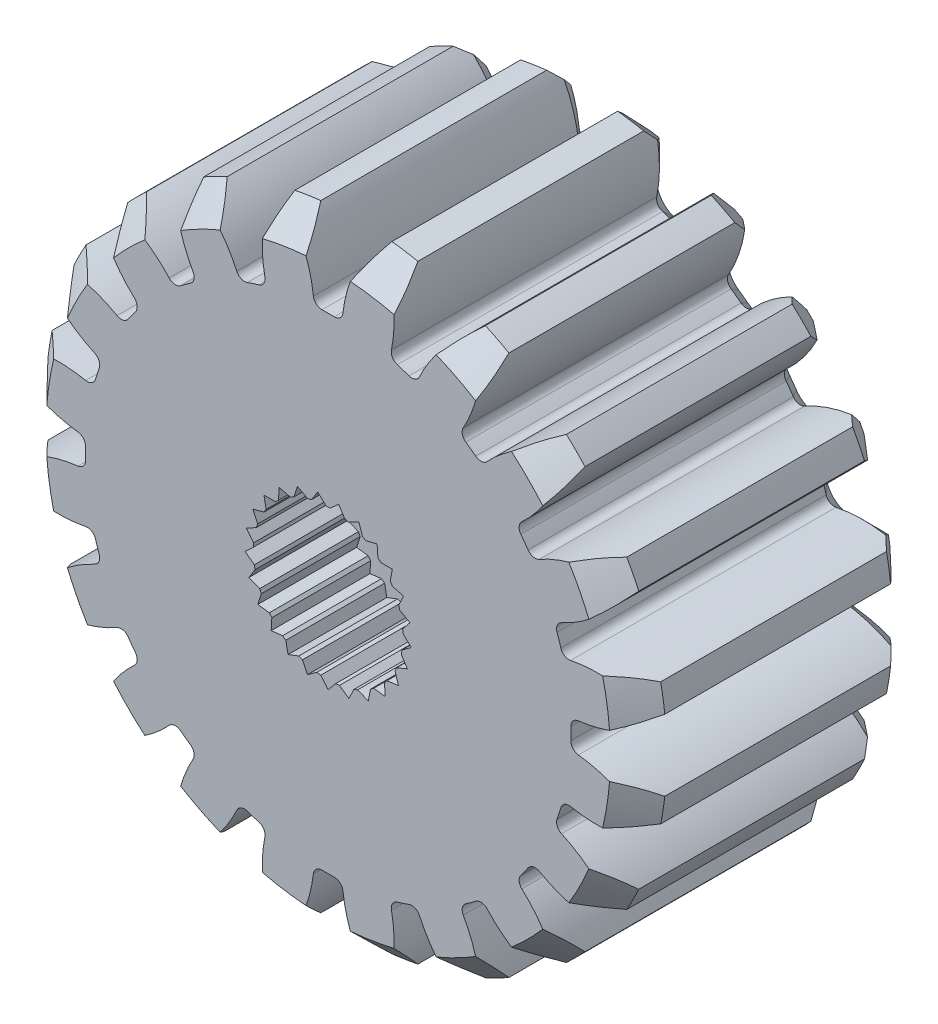
SolidWorks part; units mm, degrees
material "Plain Carbon Steel"
ref_plane "Front Plane" through (0, 0, 0) normal (0, 0, 1) x (1, 0, 0)
ref_plane "Top Plane" through (0, 0, 0) normal (0, 1, 0) x (1, 0, 0)
ref_plane "Right Plane" through (0, 0, 0) normal (1, 0, 0) x (0, 0, -1)
sketch "Sketch2" plane through (0, 0, 0) normal (0, 0, 1) x (1, 0, 0)
  circle A0 centre (0, 0) radius 10
  circle A1 centre (0, 0) radius 11
  circle A2 centre (0, 0) radius 8.6
  dimension "D1" = 20
  dimension "D2" = 22
  dimension "D3" = 2.4
extrude "Boss-Extrude1" add sketch "Sketch2" along normal mid plane 10 contours A1
sketch "Sketch3" plane through (0, 0, 0) normal (0, 0, 1) x (1, 0, 0)
  line L0 (0, 0) -> (0, 11) construction
  line L1 (-0.7846, 9.9692) -> (0.7846, 9.9692) construction
  line L2 (-0.499, 8.5855) -> (0, 0) construction
  line L3 (0, 7.8135) -> (-1.49, 11.9071) construction
  line L4 (0, 0) -> (1.7208, 10.8646) construction
  line L5 (0.7846, 9.9692) -> (2.3345, 9.7237) construction
  circle A0 centre (0, 0) radius 11 construction
  arc A1 (-2.0035, 11.8316) -> (-0.499, 8.5855) centre (-5.3628, 8.3028) cw
  arc A2 (2.0035, 11.8316) -> (0.499, 8.5855) centre (5.3628, 8.3028) ccw
  circle A3 centre (0, 0) radius 8.6 construction
  arc A4 (0.499, 8.5855) -> (-0.499, 8.5855) centre (0, 0) ccw
  circle A6 centre (0, 0) radius 10 construction
  circle A7 centre (0, 0) radius 12
  arc A8 (2.0035, 11.8316) -> (-2.0035, 11.8316) centre (0, 0) ccw
  circle A9 centre (0, 0) radius 11 construction
  dimension "D2" = 20
  dimension "D3" = 9
extrude "Cut-Extrude1" cut sketch "Sketch3" against normal through all both and the other way through all
fillet "Fillet1" radius 0.3 2 edges at (0.499, 8.5855, 0) (-0.499, 8.5855, 0)
chamfer "Chamfer1" distance 1 2 edges at (0, -11, -5) (0, -11, 5)
chamfer "Chamfer2" distance 0.6 angle 45 5 edges at (-0.6214, 9.4236, -5) (0.6214, 9.4236, -5) (-0.4218, 8.6707, -5) (0.4218, 8.6707, -5) (0, 8.6, -5)
pattern_circular "CirPattern1" count 20 over 360 about axis through (0, 0, 5) along (0, 0, -1) of "Fillet1", "Cut-Extrude1", "Chamfer2"
sketch "Sketch4" plane through (0, 0, 5) normal (0, 0, 1) x (1, 0, 0)
  line L0 (0, 0) -> (0, -4.3685) construction
  line L1 (-0.2627, -2.6369) -> (0, -2.95)
  line L2 (0.2627, -2.6369) -> (0, -2.95)
  arc A0 (-0.2627, -2.6369) -> (0.2627, -2.6369) centre (0, 0) ccw
  point P7 (0, -2.65)
  dimension "D1" = 5.3
  dimension "D2" = 80
  dimension "D3" = 0.3
extrude "Cut-Extrude2" cut sketch "Sketch4" against normal blind 3.5
pattern_circular "CirPattern2" count 25 over 360 about axis through (0, 0, 5) along (0, 0, -1) of "Cut-Extrude2"
sketch "Sketch5" plane through (0, 0, 5) normal (0, 0, 1) x (1, 0, 0)
  circle A0 centre (0, 0) radius 2.65
  arc A3 (-0.7265, 2.5485) -> (-1.215, 2.3551) centre (0, 0) ccw construction
extrude "Cut-Extrude3" cut sketch "Sketch5" against normal blind 3.5
sketch "Sketch6" plane through (0, 0, 1.5) normal (0, 0, 1) x (1, 0, 0)
  circle A0 centre (0, 0) radius 1.6
  dimension "D1" = 3.2
extrude "Cut-Extrude4" cut sketch "Sketch6" against normal through all
sketch "Sketch7" plane through (0, 0, -5) normal (0, 0, -1) x (-1, 0, 0)
  circle A0 centre (0, 0) radius 3
  dimension "D1" = 6
extrude "Cut-Extrude5" cut sketch "Sketch7" against normal blind 5
equation "\"Module\"= 1mm"
equation "\"Number of Teeth\"= 20"
equation "\"D1@Sketch2\"=\"Module\" * \"Number of Teeth\""
equation "\"D2@Sketch2\"=(\"Number of Teeth\" + 2) * \"Module\""
equation "\"D3@Sketch2\"=\"Module\" * if( \"Module\" => 1.25, 2.25, 2.4) "
equation "\"D3@Sketch3\"=180deg / \"Number of Teeth\""
equation "\"D1@Fillet1\"=0.3 * \"Module\""
equation "\"D1@CirPattern1\"=\"Number of Teeth\""
equation "\"D1@Chamfer1\"=\"Module\""
equation "\"Pressure Angle\"= 20deg"
equation "\"D2@Sketch3\"=\"Pressure Angle\""
equation "\"HubServoDiameter\"= 5.3mm"
equation "\"D1@Sketch4\"=\"HubServoDiameter\""
